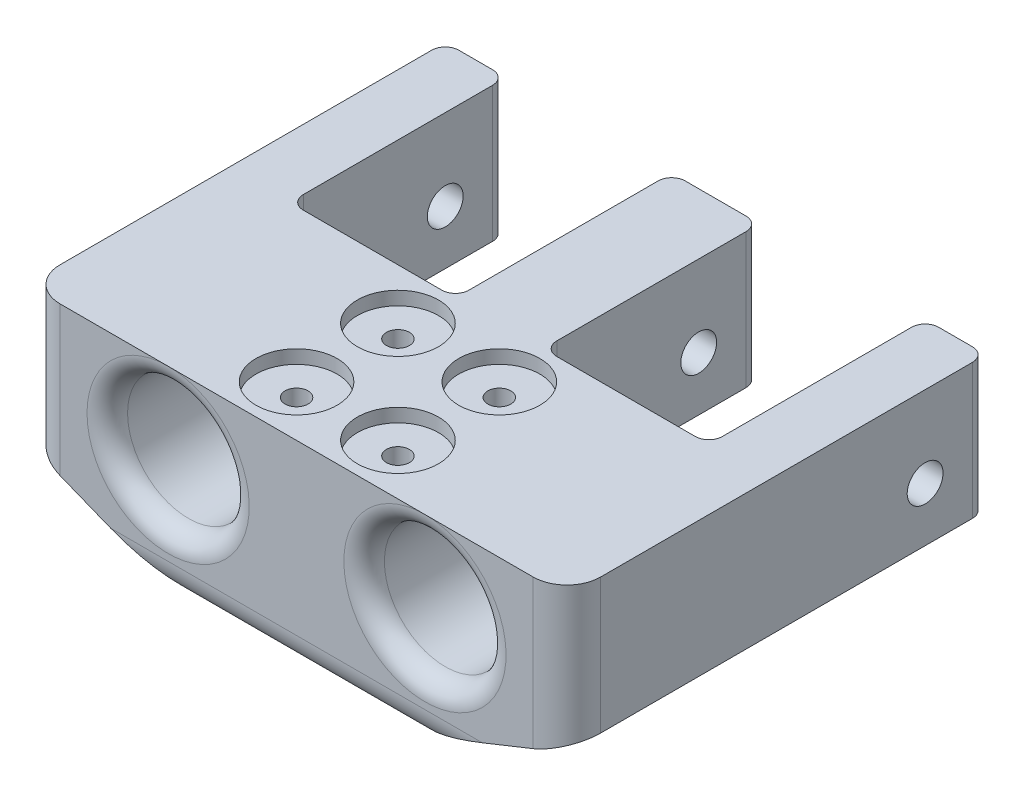
SolidWorks part; units mm, degrees
ref_plane "前视基准面" through (0, 0, 0) normal (0, 0, 1) x (1, 0, 0)
ref_plane "上视基准面" through (0, 0, 0) normal (0, 1, 0) x (1, 0, 0)
ref_plane "右视基准面" through (0, 0, 0) normal (1, 0, 0) x (0, 0, -1)
sketch "草图4" plane through (0, 0, 0) normal (0, 0, 1) x (1, 0, 0)
  line L1 (-40, -15) -> (40, -15)
  line L2 (-40, -15) -> (-40, 15)
  line L3 (-40, 15) -> (40, 15)
  line L4 (40, -15) -> (40, 15)
  line L5 (-40, -15) -> (40, 15) construction
  line L6 (-40, 15) -> (40, -15) construction
  point P0 (0, 0)
  dimension "D1" = 30
  dimension "D2" = 80
extrude "凸台-拉伸1" add sketch "草图4" along normal blind 30
sketch "草图5" plane through (0, 0, 0) normal (0, 0, -1) x (-1, 0, 0)
  line L0 (0, 0) -> (0, 50000) construction
  line L1 (-40, 15) -> (40, 15) construction
  circle A0 centre (-19, 3) radius 9
  circle A1 centre (19, 3) radius 9
  dimension "D1" = 18
  dimension "D2" = 12
  dimension "D3" = 38
extrude "切除-拉伸1" cut sketch "草图5" against normal through all
fillet "圆角2" radius 3 4 edges at (-10, 3, 30) (10, 3, 30) (-10, 3, 0) (10, 3, 0)
sketch "草图7" plane through (0, 15, 0) normal (0, 1, 0) x (1, 0, 0)
  line L0 (0, 0) -> (0, -50000) construction
  line L2 (-7.5, -22.5) -> (7.5, -22.5) construction
  line L3 (-7.5, -22.5) -> (-7.5, -7.5) construction
  line L4 (-7.5, -7.5) -> (7.5, -7.5) construction
  line L5 (7.5, -22.5) -> (7.5, -7.5) construction
  line L6 (-7.5, -22.5) -> (7.5, -7.5) construction
  line L7 (-7.5, -7.5) -> (7.5, -22.5) construction
  line L8 (-31, -30) -> (-7, -30) construction
  circle A0 centre (-7.5, -7.5) radius 1.7
  circle A1 centre (-7.5, -22.5) radius 1.7
  circle A2 centre (7.5, -22.5) radius 1.7
  circle A3 centre (7.5, -7.5) radius 1.7
  point P3 (0, -15)
  dimension "D3" = 3.4
  dimension "D4" = 15
  dimension "D1" = 15
  dimension "D2" = 15
extrude "切除-拉伸3" cut sketch "草图7" against normal through all
sketch "草图8" plane through (0, 0, 0) normal (0, 0, -1) x (-1, 0, 0)
  line L0 (-15, -15) -> (-40, -5)
  line L1 (40, -15) -> (-40, -15) construction
  line L2 (-40, -15) -> (-40, 15) construction
  line L3 (-40, -5) -> (-40, -15)
  line L4 (-40, -15) -> (-15, -15)
  line L5 (0, 0) -> (0, -50000) construction
  line L6 (40, -15) -> (15, -15)
  line L7 (40, -5) -> (40, -15)
  line L8 (15, -15) -> (40, -5)
  dimension "D1" = 30
  dimension "D2" = 10
extrude "切除-拉伸4" cut sketch "草图8" against normal through all
sketch "草图11" plane through (0, 0, 0) normal (0, 0, -1) x (-1, 0, 0)
  line L0 (-19, 15) -> (19, 15) construction
  line L1 (-6.5, 15) -> (6.5, 15)
  line L2 (-6.5, 15) -> (-6.5, -5)
  line L3 (-6.5, -5) -> (6.5, -5)
  line L4 (6.5, 15) -> (6.5, -5)
  line L5 (0, 0) -> (0, 28.8768) construction
  line L6 (31, 15) -> (31, -5)
  line L7 (-40, 15) -> (-31, 15)
  line L8 (-40, 15) -> (-40, -5)
  line L9 (-40, -5) -> (-31, -5)
  line L10 (-31, 15) -> (-31, -5)
  line L11 (40, -5) -> (31, -5)
  line L12 (40, 15) -> (40, -5)
  line L13 (40, 15) -> (31, 15)
  dimension "D1" = 13
  dimension "D2" = 9
extrude "凸台-拉伸3" add sketch "草图11" along normal blind 32
fillet "圆角5" radius 5 2 edges at (-40, 5, 30) (40, 5, 30)
fillet "圆角4" radius 5 1 edges at (0, -15, 30)
sketch "草图12" plane through (40, 0, 0) normal (1, 0, 0) x (0, 0, -1)
  line L0 (0, -15) -> (0, -5) construction
  line L1 (-25, 15) -> (32, 15) construction
  circle A0 centre (23, 3) radius 2.65
  dimension "D1" = 23
  dimension "D2" = 5.3
  dimension "D3" = 12
extrude "切除-拉伸5" cut sketch "草图12" against normal through all
fillet "圆角6" radius 2 15 edges at (35.5, -5, 0) (-35.5, -5, 0) (0, -5, 0) (-40, 5, -32) (-31, 5, -32) (-6.5, 5, -32) (6.5, 5, -32) (31, 5, -32) (40, 5, -32) (-31, 9, 0) (31, 9, 0) (-6.5, 5, 0) (-31, -1, 0) (6.5, 5, 0) (31, -1, 0)
sketch "草图14" plane through (0, 15, 0) normal (0, 1, 0) x (1, 0, 0)
  circle A0 centre (-7.5, -7.5) radius 6
  circle A1 centre (7.5, -7.5) radius 6
  circle A2 centre (7.5, -22.5) radius 6
  circle A3 centre (-7.5, -22.5) radius 6
  dimension "D1" = 12
extrude "切除-拉伸6" cut sketch "草图14" against normal blind 2
